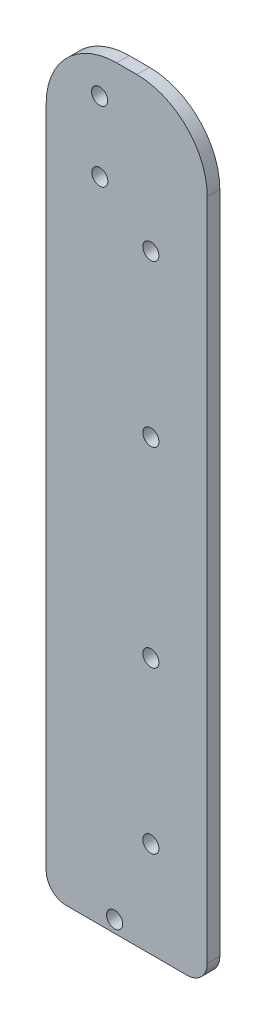
SolidWorks part; units mm, degrees
ref_plane "Front Plane" through (0, 0, 0) normal (0, 0, 1) x (1, 0, 0)
ref_plane "Top Plane" through (0, 0, 0) normal (0, 1, 0) x (1, 0, 0)
ref_plane "Right Plane" through (0, 0, 0) normal (1, 0, 0) x (0, 0, -1)
sketch "Sketch1" plane through (0, 0, 0) normal (0, 0, 1) x (1, 0, 0)
  line L1 (0, -146.6506) -> (0, 146.6506) construction
  line L3 (40.64, 5.08) -> (40.64, 172.72)
  line L5 (35.56, 0) -> (26.416, 0)
  line L7 (66.681, 0) -> (66.681, 88.9) construction
  line L8 (26.416, 0) -> (40.64, 0) construction
  line L9 (26.416, 177.8) -> (26.416, 0) construction
  line L10 (118.1346, 0) -> (-118.1346, 0) construction
  line L11 (66.681, 88.9) -> (0, 88.9) construction
  line L14 (26.416, 0) -> (5.08, 0)
  line L18 (66.681, 88.9) -> (66.681, 177.8) construction
  line L19 (66.681, 177.8) -> (0, 177.8) construction
  line L20 (0, 5.08) -> (0, 172.72)
  line L23 (26.416, 0) -> (20.32, 0) construction
  line L24 (20.32, 0) -> (19.8425, 177.8) construction
  line L25 (20.32, 0) -> (14.732, 0) construction
  line L26 (14.732, 0) -> (14.732, 8.89) construction
  line L27 (14.732, 8.89) -> (14.732, 177.8) construction
  line L28 (26.416, 24.13) -> (0, 24.13) construction
  line L35 (20.32, 0) -> (17.6513, 0) construction
  line L36 (17.6513, 0) -> (17.6513, 177.8) construction
  line L46 (17.78, 190.5) -> (22.86, 190.5)
  line L47 (19.8425, 177.8) -> (19.8425, 190.5) construction
  line L48 (19.8896, 160.274) -> (19.8425, 190.5) construction
  line L49 (19.8425, 190.5) -> (-14.4304, 190.5) construction
  line L50 (19.8896, 160.274) -> (0, 160.274) construction
  circle A0 centre (26.416, 24.13) radius 2.032
  circle A1 centre (26.416, 64.77) radius 2.032
  arc A5 (35.56, 0) -> (40.64, 5.08) centre (35.56, 5.08) ccw
  arc A6 (5.08, 0) -> (0, 5.08) centre (5.08, 5.08) cw
  circle A7 centre (26.416, 113.03) radius 2.032
  circle A8 centre (26.416, 153.67) radius 2.032
  arc A13 (40.64, 172.72) -> (22.86, 190.5) centre (22.86, 172.72) ccw
  arc A14 (0, 172.72) -> (17.78, 190.5) centre (17.78, 172.72) cw
  circle A15 centre (17.272, 3.048) radius 2.032
  circle A16 centre (13.4925, 181.102) radius 2.032
  circle A17 centre (13.531, 163.449) radius 2.032
  point P24 (0, 190.5)
  point P30 (0, 0)
  point P38 (0, 190.5)
  point P42 (0, 185.42)
  point P46 (40.64, 185.0608)
  point P52 (0, 190.5)
  dimension "D7" = 4.064
  dimension "D5" = 24.13
  dimension "D6" = 4.064
  dimension "D9" = 24.13
  dimension "D11" = 88.9
  dimension "D12" = 5.08
  dimension "D13" = 4.064
  dimension "D15" = 4.064
  dimension "D17" = 4.064
  dimension "D19" = 17.78
  dimension "D22" = 4.064
  dimension "D26" = 4.064
  dimension "D20" = 23.368
  dimension "D25" = 6.35
  dimension "D27" = 6.35
  dimension "D29" = 6.35
  dimension "D1" = 190.5
  dimension "D2" = 40.64
  dimension "D3" = 88.9
  dimension "D4" = 14.224
  dimension "D8" = 40.64
  dimension "D10" = 24.13
  dimension "D14" = 3.048
  dimension "D16" = 40.64
  dimension "D18" = 24.13
  dimension "D21" = 30.226
  dimension "D23" = 20.32
  dimension "D24" = 25.908
  dimension "D28" = 64.77
  dimension "D32" = 2.6687
  dimension "0.25" = 9.398
extrude "Boss-Extrude2" add sketch "Sketch1" along normal blind 3.175
